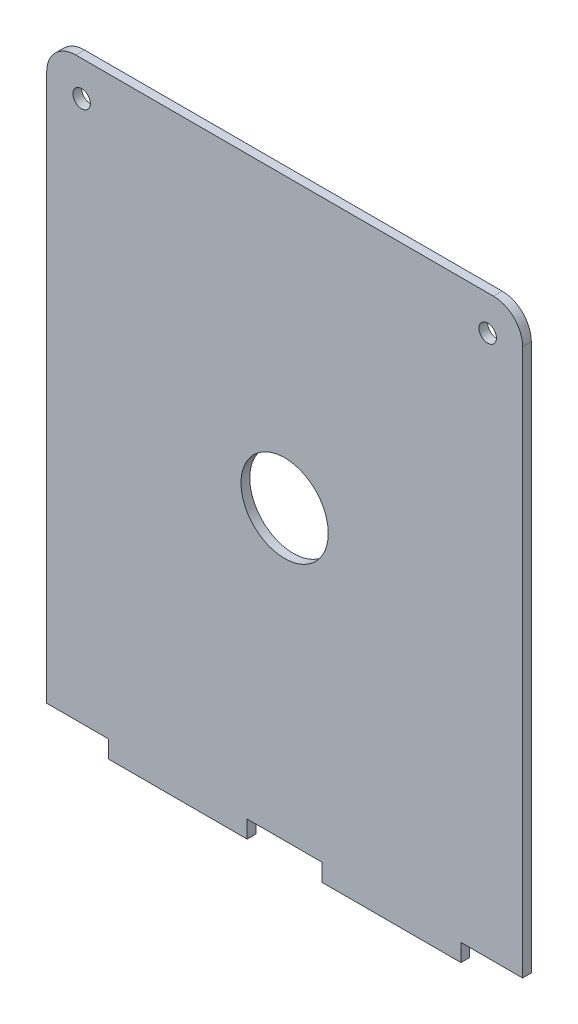
SolidWorks part; units mm, degrees
ref_plane "Front Plane" through (0, 0, 0) normal (0, 0, 1) x (1, 0, 0)
ref_plane "Top Plane" through (0, 0, 0) normal (0, 1, 0) x (1, 0, 0)
ref_plane "Right Plane" through (0, 0, 0) normal (1, 0, 0) x (0, 0, -1)
sketch "Sketch1" plane through (0, 0, 0) normal (0, 0, 1) x (1, 0, 0)
  line L1 (0, 0) -> (81.8, 0)
  line L2 (0, 0) -> (0, 102)
  line L3 (0, 102) -> (81.8, 102)
  line L4 (81.8, 0) -> (81.8, 102)
  dimension "D1" = 81.8
  dimension "D2" = 102
extrude "Boss-Extrude1" add sketch "Sketch1" along normal blind 1.5
sketch "Sketch2" plane through (0, 0, 1.5) normal (0, 0, 1) x (1, 0, 0)
  line L0 (40.9, 102) -> (40.9, 0)
  line L1 (81.8, 102) -> (0, 102) construction
  line L2 (0, 0) -> (81.8, 0) construction
  line L3 (81.8, 0) -> (81.8, 3)
  line L4 (0, 0) -> (10.6, 0)
  line L5 (0, 0) -> (0, 3)
  line L6 (0, 3) -> (10.6, 3)
  line L7 (10.6, 0) -> (10.6, 3)
  line L8 (34.455, 0) -> (47.345, 0)
  line L9 (34.455, 0) -> (34.455, 3)
  line L10 (34.455, 3) -> (47.345, 3)
  line L11 (47.345, 0) -> (47.345, 3)
  line L12 (81.8, 0) -> (71.2, 0)
  line L13 (71.2, 0) -> (71.2, 3)
  line L14 (81.8, 3) -> (71.2, 3)
  line L15 (0, 102) -> (0, 0) construction
  circle A0 centre (6, 96) radius 1.5
  circle A1 centre (75.8, 96) radius 1.5
  line M8 (0, 102) -> (0, 0)
  line M9 (0, 0) -> (81.8, 0)
  line M10 (81.8, 0) -> (81.8, 102)
  dimension "D5" = 6
  dimension "D1" = 3
  dimension "D2" = 10.6
  dimension "D3" = 12.89
  dimension "D4" = 6.445
  dimension "D6" = 6
extrude "Cut-Extrude1" cut sketch "Sketch2" against normal through all contours L7 L6 M9 M8 | L11 L10 L0 M9 | L10 L9 L0 M9 | L14 L13 M10 M9 | A0 | A1 region at (44.1225, 1.5, 1.5) region at (37.6775, 1.5, 1.5) region at (76.5, 1.5, 1.5) region at (5.3, 1.5, 1.5)
sketch "Sketch3" plane through (0, 0, 1.5) normal (0, 0, 1) x (1, 0, 0)
  line L0 (0, 33.6536) -> (81.8, 33.6536)
  line L1 (0, 102) -> (0, 3) construction
  line L2 (81.8, 3) -> (81.8, 102) construction
  line L3 (40.9, 102) -> (40.9, 3)
  line L4 (81.8, 102) -> (0, 102) construction
  line L5 (34.455, 3) -> (47.345, 3) construction
  line L6 (35.4, 39.1536) -> (46.4, 39.1536)
  line L7 (35.4, 28.1536) -> (46.4, 28.1536)
  circle A0 centre (35.4, 33.6536) radius 5.5
  circle A1 centre (46.4, 33.6536) radius 5.5
  point P19 (40.9, 28.1536)
  point P20 (40.9, 39.1536)
  dimension "D1" = 5.5
  dimension "D2" = 11
  dimension "D3" = 68.3464
extrude "Cut-Extrude2" [suppressed] cut sketch "Sketch3" against normal through all contours L0 A0 | L0 A0 | A1 L0 | A1 L0 | A0 L7 L3 | L7 A1 L3 | L3 A1 L6 | A0 L3 L6
fillet "Fillet1" radius 5 2 edges at (81.8, 102, 0.75) (0, 102, 0.75)
sketch "Sketch4" plane through (0, 0, 1.5) normal (0, 0, 1) x (1, 0, 0)
  line L0 (40.9, 102) -> (40.9, 3)
  line L1 (76.8, 102) -> (5, 102) construction
  line L2 (34.455, 3) -> (47.345, 3) construction
  circle A0 centre (40.9, 52.5) radius 7.5
  dimension "D1" = 15
extrude "Cut-Extrude3" cut sketch "Sketch4" against normal blind 10 contours L0 A0 | L0 A0 region at (44.0831, 52.5, 1.5) region at (37.7169, 52.5, 1.5)
